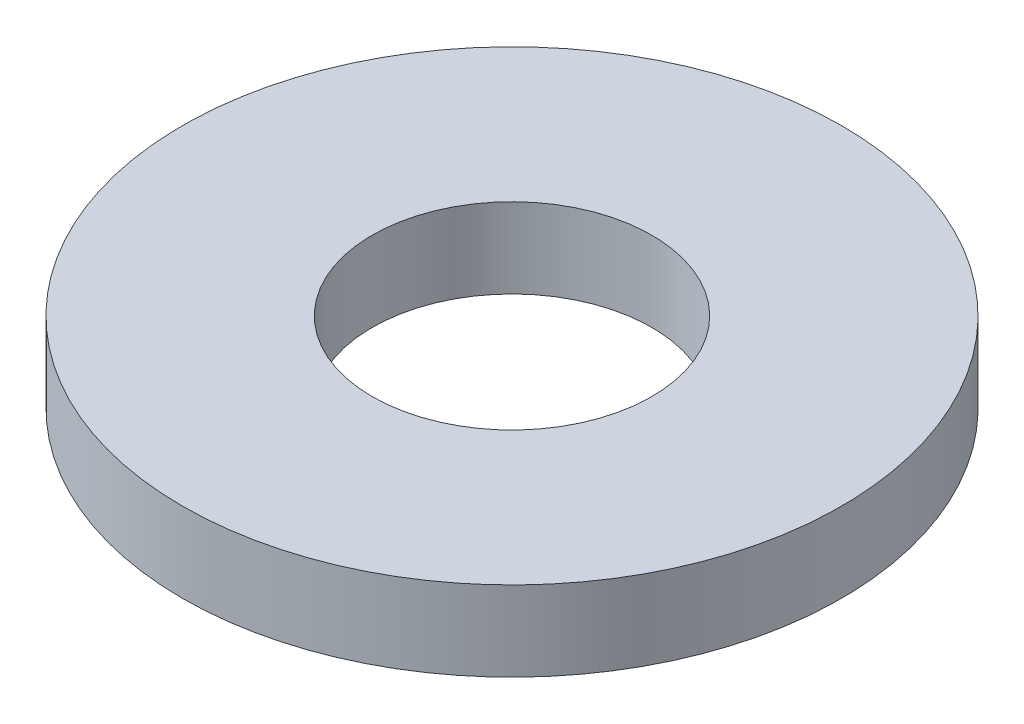
SolidWorks part; units mm, degrees
ref_plane "Front Plane" through (0, 0, 0) normal (0, 0, 1) x (1, 0, 0)
ref_plane "Top Plane" through (0, 0, 0) normal (0, 1, 0) x (1, 0, 0)
ref_plane "Right Plane" through (0, 0, 0) normal (1, 0, 0) x (0, 0, -1)
sketch "Sketch1" plane through (0, 0, 0) normal (0, 1, 0) x (1, 0, 0)
  circle A0 centre (0, 0) radius 82.5
  dimension "FLANGE_OD" = 165
extrude "Boss-Extrude1" add sketch "Sketch1" along normal blind 20
sketch "Sketch2" plane through (0, 0, 0) normal (0, 1, 0) x (1, 0, 0)
  circle A0 centre (0, 0) radius 35
  dimension "BORE_D" = 70
extrude "Cut-Extrude1" cut sketch "Sketch2" along normal through all
sketch "Sketch3" plane through (0, 20, 0) normal (0, 1, 0) x (1, 0, 0)
  circle A0 centre (0, 0) radius 30.9318 construction
  circle A1 centre (-30.9318, 0) radius 3.439
  dimension "BOLT_D" = 6.878
  dimension "BOLT_PCD" = 61.8635
extrude "Cut-Extrude2" cut sketch "Sketch3" against normal blind 12.2789 rebuild error yes
pattern_circular "CirPattern1" count 3 over 360 rebuild error yes
